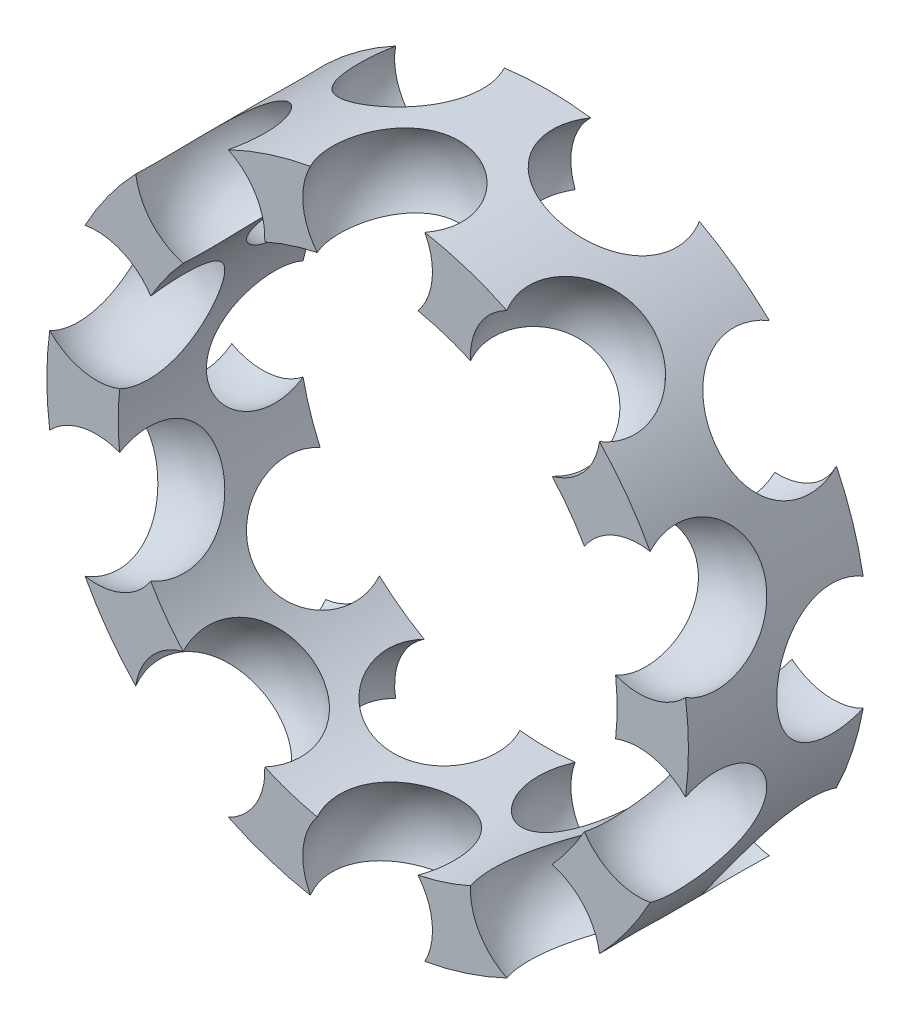
SolidWorks part; units mm, degrees
material "Простая углеродистая сталь"
ref_plane "Спереди" through (0, 0, 0) normal (0, 0, 1) x (1, 0, 0)
ref_plane "Сверху" through (0, 0, 0) normal (0, 1, 0) x (1, 0, 0)
ref_plane "Справа" through (0, 0, 0) normal (1, 0, 0) x (0, 0, -1)
sketch "Эскиз1" plane through (0, 0, 0) normal (1, 0, 0) x (0, 0, -1)
  line L0 (0, 0) -> (50000, 0) construction
  line L1 (0, 7.3125) -> (4.5, 7.3125)
  line L2 (0, 7.3125) -> (0, 5.6875)
  line L3 (0, 5.6875) -> (4.5, 5.6875)
  line L4 (4.5, 7.3125) -> (4.5, 5.6875)
  dimension "D1" = 4.5
  dimension "D2" = 5.6875
  dimension "D3" = 7.3125
revolve "Повернуть1" add sketch "Эскиз1" angle 360 about L0
ref_plane "Плоскость1" through (0, 6.5, 0) normal (0, 1, 0) x (1, 0, 0)
sketch "Эскиз2" plane through (0, 6.5, 0) normal (0, 1, 0) x (1, 0, 0)
  line L0 (0, 2.5) -> (0, -0.75)
  arc A0 (0, -0.75) -> (0, 2.5) centre (0, 0.875) ccw
  dimension "D1" = 3.25
  dimension "D2" = 0.875
revolve "Вырез-Повернуть1" cut sketch "Эскиз2" angle 360 about L0
pattern_circular "Круговой массив1" count 10 over 360 about axis through (0, 0, 0) along (0, 0, 1) of "Вырез-Повернуть1" reverse direction yes
ref_plane "Плоскость2" through (-2.2597, 6.9546, 0) normal (-0.309, 0.9511, 0) x (0, 0, 1)
ref_plane "Плоскость3" through (-2.0086, 6.1819, 0) normal (-0.309, 0.9511, 0) x (0, 0, 1)
sketch "Эскиз3" plane through (-2.0086, 6.1819, 0) normal (-0.309, 0.9511, 0) x (0, 0, 1)
  line L0 (-4.5, 7.3125) -> (-4.5, -7.3125) construction
  line L1 (-5.245, 0) -> (-1.995, 0)
  arc A0 (-1.995, 0) -> (-5.245, 0) centre (-3.62, 0) ccw
  dimension "D1" = 3.25
  dimension "D2" = 0.88
revolve "Вырез-Повернуть2" cut sketch "Эскиз3" angle 360 about L1
pattern_circular "Круговой массив2" count 10 over 360 about axis through (0, 0, 0) along (0, 0, 1) of "Вырез-Повернуть2"
sketch "Эскиз4" plane through (0, 0, 0) normal (0, 0, 1) x (1, 0, 0)
  circle A0 centre (0, 0) radius 7.3125
  dimension "D1" = 14.625
extrude "Вырез-Вытянуть1" cut sketch "Эскиз4" against normal blind 0.2
ref_plane "Плоскость4" through (0, 0, -2.25) normal (0, 0, 1) x (1, 0, 0)
mirror "Зеркальное отражение1" about plane through (0, 0, -2.25) normal (0, 0, 1) of "Вырез-Вытянуть1"
